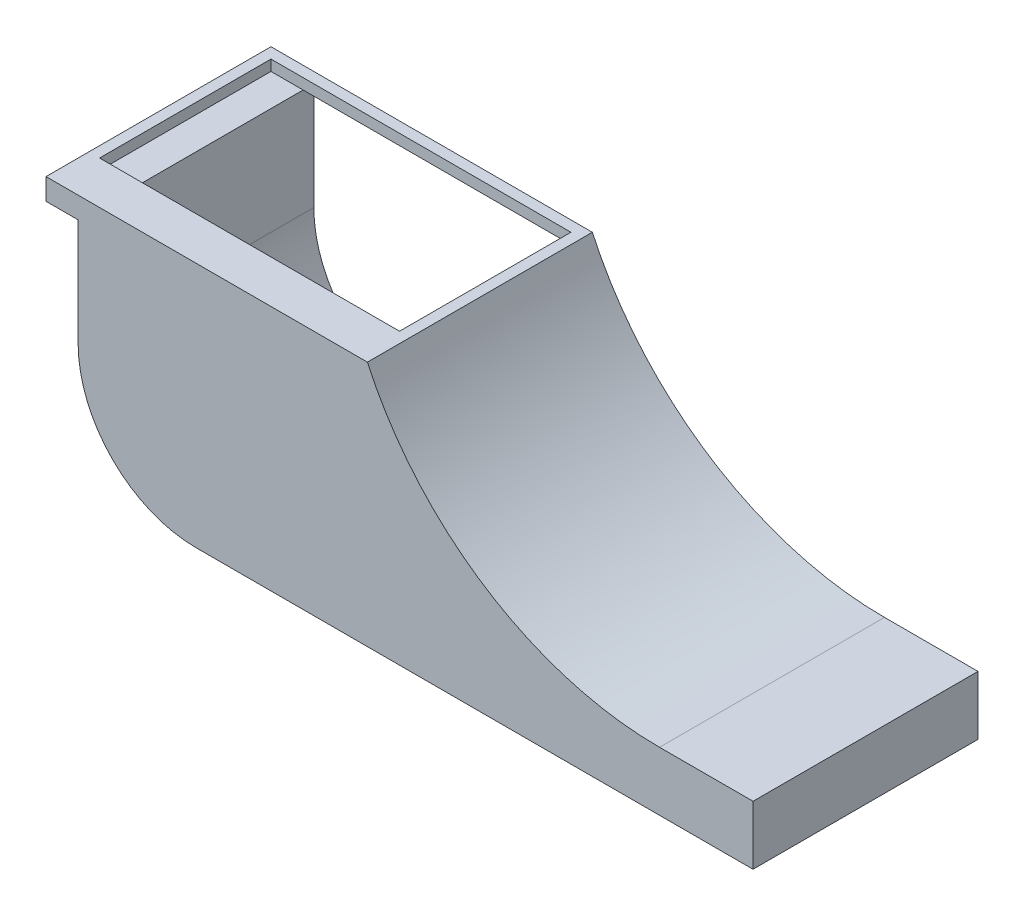
SolidWorks part; units mm, degrees
ref_plane "Front Plane" through (0, 0, 0) normal (0, 0, 1) x (1, 0, 0)
ref_plane "Top Plane" through (0, 0, 0) normal (0, 1, 0) x (1, 0, 0)
ref_plane "Right Plane" through (0, 0, 0) normal (1, 0, 0) x (0, 0, -1)
sketch "Sketch1" plane through (0, 0, 0) normal (0, 0, 1) x (1, 0, 0)
  line L1 (33, -11.5) -> (-33, -11.5)
  line L2 (33, -11.5) -> (33, 11.5)
  line L3 (33, 11.5) -> (-33, 11.5)
  line L4 (-33, -11.5) -> (-33, 11.5)
  line L5 (33, -11.5) -> (-33, 11.5) construction
  line L6 (33, 11.5) -> (-33, -11.5) construction
  point P0 (0, 0)
  dimension "D1" = 66
  dimension "D2" = 23
extrude "body" add sketch "Sketch1" along normal blind 21
sketch "Sketch2" plane through (0, 0, 21) normal (0, 0, 1) x (1, 0, 0)
  line L1 (33, 11.5) -> (-3, 11.5)
  line L2 (33, 11.5) -> (33, -6)
  line L3 (33, -6) -> (-3, -6)
  line L4 (-3, 11.5) -> (-3, -6)
  dimension "D1" = 36
  dimension "D2" = 17.5
extrude "remove_material" cut sketch "Sketch2" against normal through all
sketch "Sketch3" plane through (0, 0, 0) normal (0, 0, -1) x (-1, 0, 0)
  line L0 (32, -10.5) -> (-32, -10.5)
  line L1 (-32, -10.5) -> (-32, -7)
  line L2 (-32, -7) -> (4, -7)
  line L3 (4, -7) -> (4, 10.5)
  line L4 (4, 10.5) -> (32, 10.5)
  line L5 (32, 10.5) -> (32, -10.5)
  line L6 (33, -11.5) -> (-33, -11.5) construction
  line L7 (33, 11.5) -> (33, -11.5) construction
  line L8 (3, 11.5) -> (33, 11.5) construction
  line L9 (3, 11.5) -> (3, -6) construction
  line L10 (3, -6) -> (-33, -6) construction
  line L11 (-33, -11.5) -> (-33, -6) construction
  dimension "D1" = 1
  dimension "D2" = 1
  dimension "D3" = 1
  dimension "D4" = 1
  dimension "D5" = 1
  dimension "D6" = 1
extrude "ducting" cut sketch "Sketch3" against normal blind 20
sketch "Sketch4" plane through (0, 11.5, 0) normal (0, 1, 0) x (1, 0, 0)
  line L0 (-3, -10.5) -> (-33, -10.5) construction
  line L1 (-3, 0) -> (-3, -21) construction
  line L2 (-33, -21) -> (-33, 0) construction
  line L4 (-3, -21) -> (-33, -21) construction
  line L5 (-18, -21) -> (-18, 0) construction
  line L6 (-3, 0) -> (-33, 0) construction
  line L7 (-32, -1) -> (-4, -1)
  line L8 (-32, -1) -> (-32, -20)
  line L9 (-32, -20) -> (-4, -20)
  line L10 (-4, -1) -> (-4, -20)
  line L11 (-32, -1) -> (-4, -20) construction
  line L12 (-32, -20) -> (-4, -1) construction
  point P6 (-18, -10.5)
  dimension "D1" = 1
  dimension "D2" = 1
extrude "inlet" cut sketch "Sketch4" against normal blind 1
sketch "Sketch5" plane through (0, -11.5, 0) normal (0, -1, 0) x (1, 0, 0)
  line L0 (33, 21) -> (33, 0) construction
  line L1 (32, 1) -> (-13, 1)
  line L2 (32, 1) -> (32, 20)
  line L3 (32, 20) -> (-13, 20)
  line L4 (-13, 1) -> (-13, 20)
  line L5 (-33, 0) -> (33, 0) construction
  line L6 (-33, 21) -> (33, 21) construction
  dimension "D1" = 1
  dimension "D2" = 1
  dimension "D3" = 45
  dimension "D4" = 1
extrude "main_outlet" cut sketch "Sketch5" against normal blind 1
fillet "Fillet1" radius 30 1 edges at (-3, -6, 10.5)
fillet "Fillet2" radius 30 1 edges at (-4, -7, 10)
sketch "Sketch6" plane through (-33, 0, 0) normal (-1, 0, 0) x (0, 0, 1)
  line L0 (21, 11.5) -> (21, -11.5) construction
  line L1 (20, -0.5) -> (18.5, -0.5)
  line L2 (20, -0.5) -> (20, -8.5)
  line L3 (20, -8.5) -> (18.5, -8.5)
  line L4 (18.5, -0.5) -> (18.5, -8.5)
  line L5 (21, -11.5) -> (0, -11.5) construction
  dimension "D1" = 1.5
  dimension "D2" = 8
  dimension "D3" = 1
  dimension "D4" = 3
extrude "batt_outlet" [suppressed] cut sketch "Sketch6" against normal blind 1
sketch "Sketch8" plane through (0, 0, 20) normal (0, 0, -1) x (-1, 0, 0)
  line L0 (3, 11.5) -> (33, 11.5) construction
  line L1 (32, 11.5) -> (3.5635, 11.5)
  line L2 (32, 11.5) -> (32, 10.5)
  line L3 (32, 10.5) -> (3.5635, 10.5)
  line L4 (3.5635, 11.5) -> (3.5635, 10.5)
  line L5 (32, -10.5) -> (32, 11.5) construction
extrude "fan_block" add sketch "Sketch8" along normal blind 3
fillet "Fillet9" radius 5 1 edges at (32, -7, 10)
sketch "Sketch10" plane through (0, 0, 20) normal (0, 0, -1) x (-1, 0, 0)
  line L0 (32, -10.5) -> (32, 10.5) construction
  line L1 (32, 10.5) -> (29, 10.5)
  line L2 (32, 10.5) -> (32, -10.5)
  line L3 (32, -10.5) -> (29, -10.5)
  line L4 (29, 10.5) -> (29, -10.5)
  line L5 (-31.7948, -10.5) -> (32, -10.5) construction
  dimension "D1" = 3
  dimension "D2" = 21
extrude "add_int_material" add sketch "Sketch10" along normal blind 20
sketch "Sketch11" plane through (-33, 0, 0) normal (-1, 0, 0) x (0, 0, 1)
  line L0 (21, 11.5) -> (21, -11.5) construction
  line L1 (0, -11.5) -> (21, -11.5)
  line L2 (0, -11.5) -> (0, 9.5)
  line L3 (0, 9.5) -> (21, 9.5)
  line L4 (21, -11.5) -> (21, 9.5)
  dimension "D1" = 21
extrude "remove_outside" cut sketch "Sketch11" against normal blind 3
fillet "Fillet11" radius 11 2 edges at (-30, -11.5, 10.5) (-29, -10.5, 10)
